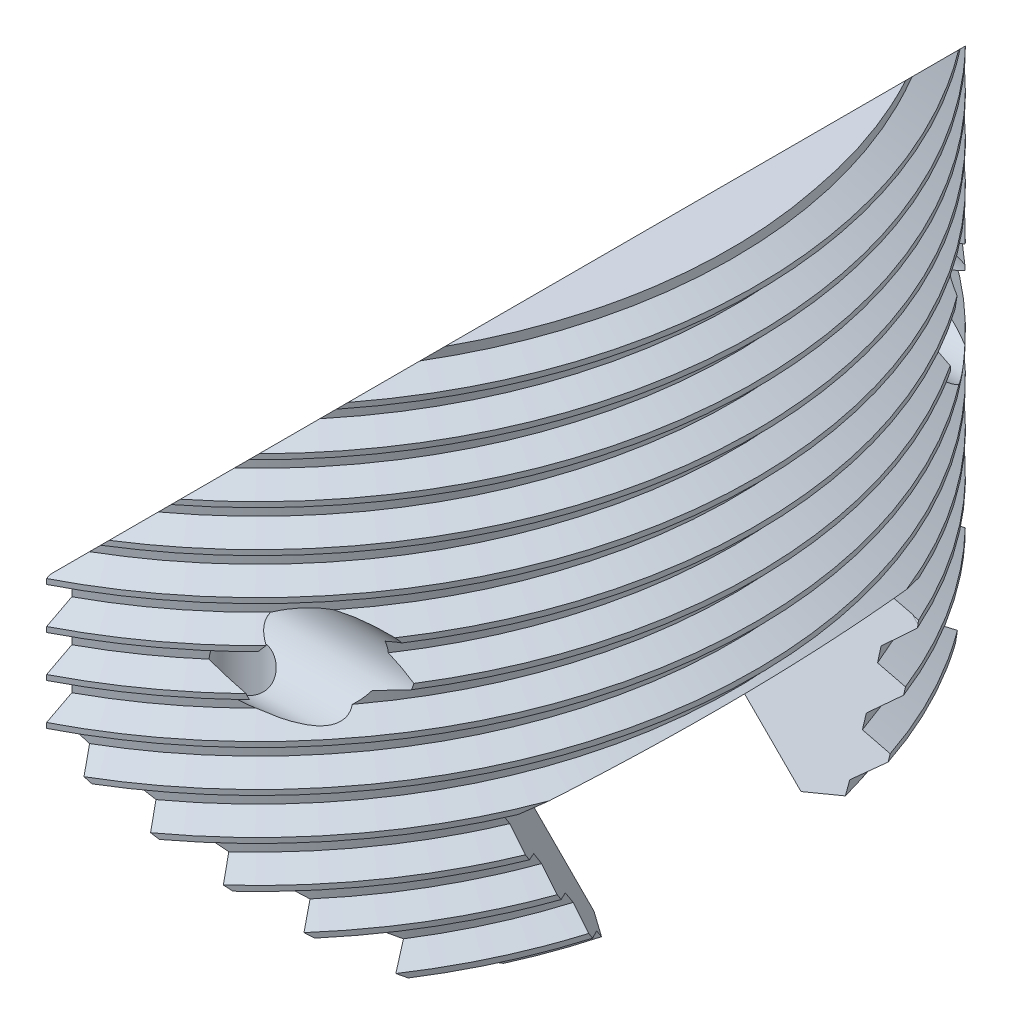
SolidWorks part; units mm, degrees
ref_plane "Front Plane" through (0, 0, 0) normal (0, 0, 1) x (1, 0, 0)
ref_plane "Top Plane" through (0, 0, 0) normal (0, 1, 0) x (1, 0, 0)
ref_plane "Right Plane" through (0, 0, 0) normal (1, 0, 0) x (0, 0, -1)
sketch "Sketch1" plane through (0, 0, 0) normal (0, 1, 0) x (1, 0, 0)
  circle A0 centre (0, 0) radius 25
extrude "Boss-Extrude1" add sketch "Sketch1" along normal blind 28
thread "Thread1" pitch 2.1167 method cut profile "Thread Profile1" start angle 0, offset 5, length 0, pitch 2.1167, diameter 50
ref_plane "Plane1" through (25, -5, 0) normal (0, 0, 1) x (1, 0, 0)
sketch "Thread Profile1" plane through (25, -5, 0) normal (0, 0, 1) x (1, 0, 0)
  line L0 (0, 0) -> (0, 2.1167) construction
  line L11 (0, 0) -> (0, 1.8521)
  line L12 (0, 1.8521) -> (-1.1457, 1.1906)
  line L13 (-1.1457, 1.1906) -> (-1.1457, 0.6615)
  line L15 (-1.1457, 0.6615) -> (0, 0)
  line L17 (-1.1457, 0.926) -> (0, 0.926) construction
  point P2 (0, 0)
  dimension "Pitch" = 2.1167
  dimension "Profile_Angle" = 60
  dimension "Profile_Land" = 0.5292
  dimension "Profile_Height" = 1.1457
sketch "Sketch5" plane through (0, 0, 0) normal (0, 1, 0) x (1, 0, 0)
  line L0 (0, 25) -> (0, -25) construction
  line L1 (0, 0) -> (11, 0) construction
  line L2 (0, 0) -> (21, 0) construction
  line L3 (21, 0) -> (21, 13.5647) construction
  line L4 (21, 13.5647) -> (21, -13.5647) construction
  line L7 (11, 0) -> (11, 22.4499)
  line L8 (11, 0) -> (11, -22.4499)
  circle A0 centre (0, 0) radius 25 construction
  circle A2 centre (0, 0) radius 25 construction
  dimension "D7" = 50
  dimension "D3" = 11
ref_plane "Plane2" through (11, 0, 0) normal (1, 0, 0) x (0, 0, -1)
other "SurfaceCut1"
ref_plane "Plane3" through (0, 28, 0) normal (0, 1, 0) x (1, 0, 0)
ref_plane "Plane4" through (10.5, 10.5, 0) normal (0.7071, 0.7071, 0) x (0, 0, -1)
ref_plane "Plane11" through (10.8536, 10.8536, 0) normal (0.7071, 0.7071, 0) x (0, 0, -1)
sketch "Sketch6" plane through (0, 28, 0) normal (0, 1, 0) x (1, 0, 0)
  line L0 (21, 13.5647) -> (21, -13.5647) construction
  line L1 (21, 0) -> (0, 0) construction
ref_plane "Plane5" through (-3.5, 3.5, 0) normal (0.7071, -0.7071, 0) x (0, 0, 1)
ref_plane "Plane6" through (10.5, -10.5, 0) normal (0.7071, -0.7071, 0) x (0, 0, -1)
other "SurfaceCut2"
other "SurfaceCut3"
sketch "Sketch7" plane through (10.5, -10.5, 0) normal (0.7071, -0.7071, 0) x (0, 0, -1)
  line L0 (0, 14.8492) -> (4.775, 14.8492)
  line L1 (0, 14.8492) -> (13.5647, 14.8492) construction
  line L2 (4.775, 14.8492) -> (10.0783, 20.1525)
  line L4 (-10.0783, 20.1525) -> (-4.775, 14.8492)
  line L5 (13.5647, 14.8492) -> (-13.5647, 14.8492) construction
  line L6 (-4.775, 14.8492) -> (0, 14.8492)
  line L9 (18.2224, 14.8492) -> (-18.2224, 14.8492) construction
  line L10 (-10.0783, 20.1525) -> (0, 20.1525)
  line L11 (0, 34.6482) -> (0, 19.799) construction
  line L12 (0, 20.1525) -> (10.0783, 20.1525)
  dimension "D1" = 7.5
  dimension "D3" = 45
  dimension "D4" = 45
  dimension "D6" = 4.775
extrude "Cut-Extrude1" cut sketch "Sketch7" against normal through all both and the other way through all
ref_plane "Plane7" through (21.6614, -0.1268, -0.1787) normal (-0.9999, 0.0059, 0.0082) x (0.0082, -0.0009, 1)
sketch "Sketch8" plane through (21.6614, -0.1268, -0.1787) normal (-0.9999, 0.0059, 0.0082) x (0.0082, -0.0009, 1)
  line L5 (5.4537, 0.132) -> (10.2512, 6.8506)
  line L6 (10.2512, 6.8506) -> (-9.9063, 6.9968)
  line L7 (5.4537, 0.132) -> (-4.5621, 0.2046)
  line L8 (-4.5621, 0.2046) -> (-9.9063, 6.9968)
extrude "Cut-Extrude2" cut sketch "Sketch8" against normal blind 28 draft 30 draft outward yes
ref_plane "Plane8" through (11, 0, 0) normal (-1, 0, 0) x (0, 0, 1)
sketch "Sketch10" plane through (11, 0, 0) normal (-1, 0, 0) x (0, 0, 1)
  line L0 (0, 0) -> (0, 28.7071) construction
  line L1 (0, 14.3536) -> (25.4236, 14.3536) construction
  line L2 (-16, 14.3536) -> (0, 14.3536)
  line L3 (-16, 18) -> (-16, 10.7071) construction
  line L4 (22.2724, 18) -> (-21.6942, 18) construction
  line L5 (-21.4418, 10.7071) -> (-5.275, 10.7071) construction
  line L6 (16, 18) -> (16, 10.7071) construction
  line L7 (5.275, 10.7071) -> (21.3014, 10.7071) construction
  line L8 (0, 14.3536) -> (16, 14.3536)
  circle A0 centre (-16, 14.3536) radius 1.25
  circle A1 centre (16, 14.3536) radius 1.25
  point P17 (16, 14.3536)
  dimension "D1" = 2.5
  dimension "D2" = 16
hole_wizard "Tap Drill for M5x0.8 Tap2" positions "Sketch25" profile "Sketch26" hole size "M5x0.8" standard "ANSI Metric" end condition through all
sketch "Sketch25" plane through (11, 0, 0) normal (-1, 0, 0) x (0, 0, 1)
  point P0 (-16, 14.3536)
  point P3 (16, 14.3536)
sketch "Sketch26" plane through (11, 14.3536, -16) normal (0, 1, 0) x (0, 0, 1)
  line L0 (0, 0) -> (0, 14.0558)
  line L1 (0, 14.0558) -> (2.1, 14.0558)
  line L2 (2.1, 14.0558) -> (2.1, 0)
  line L5 (2.1, 0) -> (0, 0)
  line L11 (0, -6.35) -> (0, 107.95) construction
  dimension "Thru Hole Dia." = 4.2
  dimension "Thru Hole Depth" = 14.0558
ref_plane "Plane9" through (0, 28, 0) normal (0, 1, 0) x (1, 0, 0)
sketch "Sketch28" plane through (0, 28, 0) normal (0, 1, 0) x (1, 0, 0)
  line L0 (11, 0) -> (11, 16)
  line L1 (11, 0) -> (11, 22.4499) construction
  line L2 (11, 0) -> (11, -16)
  line L3 (11, 0) -> (11, -22.4499) construction
  line L4 (11, 16) -> (11, 0) construction
  line L5 (11, 16) -> (14, 16)
  line L6 (11, -16) -> (14, -16)
  circle A0 centre (14, 16) radius 1.5875
  circle A1 centre (14, -16) radius 1.5875
  dimension "D1" = 3
  dimension "D2" = 3.175
extrude "Cut-Extrude3" cut sketch "Sketch28" against normal through all both and the other way through all contours A1 | A0
ref_plane "Plane10" through (11.0303, 11.0303, 0) normal (-0.7071, -0.7071, 0) x (-0.7071, 0.7071, 0)
sketch "Sketch29" plane through (11, 0, 0) normal (-1, 0, 0) x (0, 0, 1)
  circle A0 centre (-16, 14.3536) radius 2.3813
  dimension "D1" = 4.7625
extrude "Cut-Extrude4" cut sketch "Sketch29" against normal blind 10
sketch "Sketch30" plane through (11, 0, 0) normal (-1, 0, 0) x (0, 0, 1)
  circle A0 centre (16, 14.3536) radius 2.3813
  dimension "D1" = 4.7625
extrude "Cut-Extrude5" cut sketch "Sketch30" against normal blind 10
